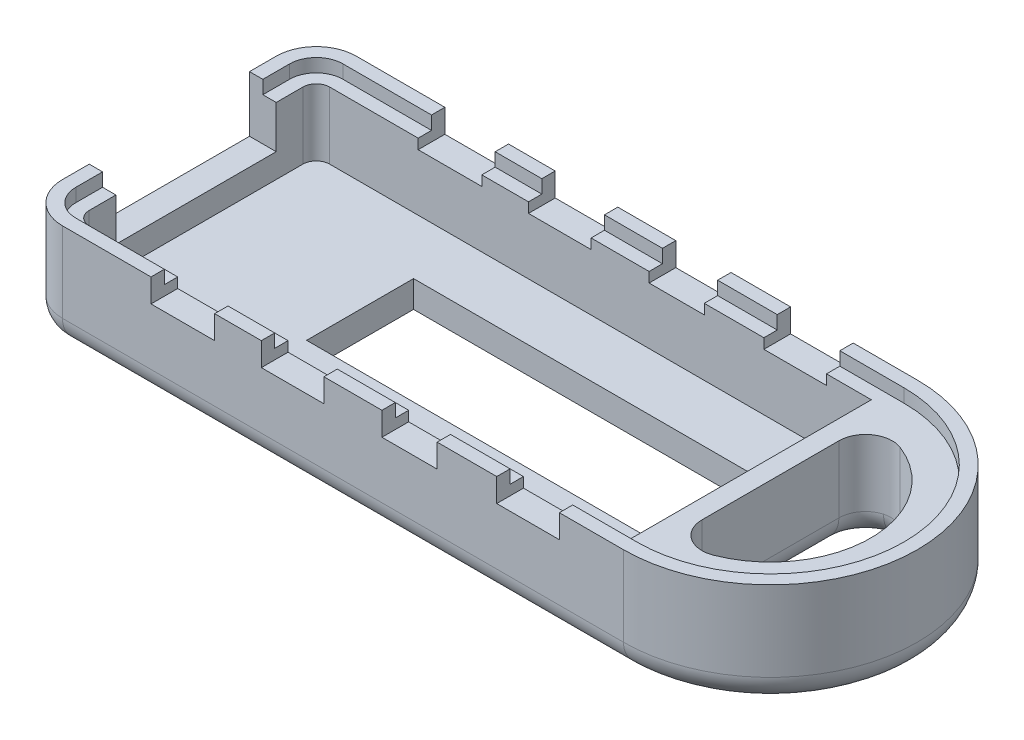
SolidWorks part; units mm, degrees
material "ABS"
ref_plane "Спереди" through (0, 0, 0) normal (0, 0, 1) x (1, 0, 0)
ref_plane "Сверху" through (0, 0, 0) normal (0, 1, 0) x (1, 0, 0)
ref_plane "Справа" through (0, 0, 0) normal (1, 0, 0) x (0, 0, -1)
sketch "Эскиз1" plane through (0, 0, 0) normal (0, 1, 0) x (1, 0, 0)
  line L0 (6.6974, 8.3377) -> (6.6974, -13.6623) construction
  line L1 (-35.3026, 8.3377) -> (6.6974, 8.3377)
  line L2 (-38.3026, 5.3377) -> (-38.3026, -10.6623)
  line L3 (-35.3026, -13.6623) -> (6.6974, -13.6623)
  arc A1 (-38.3026, -10.6623) -> (-35.3026, -13.6623) centre (-35.3026, -10.6623) ccw
  arc A2 (-38.3026, 5.3377) -> (-35.3026, 8.3377) centre (-35.3026, 5.3377) cw
  arc A4 (6.6974, 8.3377) -> (6.6974, -13.6623) centre (6.6974, -2.6623) cw
  point P3 (0, 0)
  point P5 (0, 0)
  point P6 (12.6974, -13.6623)
  point P9 (-38.3026, -13.6623)
  point P12 (-38.3026, 8.3377)
  point P14 (0, 0)
  dimension "D1" = 45
  dimension "D2" = 22
extrude "Бобышка-Вытянуть1" add sketch "Эскиз1" along normal blind 7
sketch "Эскиз2" plane through (0, 7, 0) normal (0, 1, 0) x (1, 0, 0)
  line L8 (-36.3026, 5.3377) -> (-36.3026, -10.6623)
  line L9 (-35.3026, -11.6623) -> (6.6974, -11.6623)
  line L11 (6.6974, 6.3377) -> (-35.3026, 6.3377)
  line L12 (-36.3026, 5.3377) -> (-36.3026, -10.6623)
  line L13 (-35.3026, -11.6623) -> (6.6974, -11.6623)
  line L15 (6.6974, 6.3377) -> (-35.3026, 6.3377)
  arc A3 (6.6974, -11.6623) -> (6.6974, 6.3377) centre (6.6974, -2.6623) ccw
  arc A4 (6.6974, -11.6623) -> (6.6974, 6.3377) centre (6.6974, -2.6623) ccw
  arc A8 (-35.3026, 6.3377) -> (-36.3026, 5.3377) centre (-35.3026, 5.3377) ccw
  arc A9 (-35.3026, 6.3377) -> (-36.3026, 5.3377) centre (-35.3026, 5.3377) ccw
  arc A10 (-36.3026, -10.6623) -> (-35.3026, -11.6623) centre (-35.3026, -10.6623) ccw
  arc A11 (-36.3026, -10.6623) -> (-35.3026, -11.6623) centre (-35.3026, -10.6623) ccw
  dimension "D1" = 2
extrude "Вырез-Вытянуть1" cut sketch "Эскиз2" against normal blind 5
sketch "Эскиз3" plane through (0, 2, 0) normal (0, 1, 0) x (1, 0, 0)
  line L0 (6.6974, 8.3377) -> (6.6974, -13.6623) construction
  line L1 (-24.7416, 2.0578) -> (1.7446, 2.0578)
  line L2 (-24.7416, 2.0578) -> (-24.7416, -5.9479)
  line L3 (-24.7416, -5.9479) -> (1.7446, -5.9479)
  line L4 (1.7446, 2.0578) -> (1.7446, -5.9479)
  line L5 (6.6974, 2.4612) -> (6.6974, -7.7858)
  arc A3 (9.4246, 4.3243) -> (9.4246, -9.6488) centre (6.6974, -2.6623) cw
  arc A5 (6.6974, -7.7858) -> (9.4246, -9.6488) centre (8.6974, -7.7858) ccw
  arc A6 (6.6974, 2.4612) -> (9.4246, 4.3243) centre (8.6974, 2.4612) cw
  point P11 (6.6974, -10.1623)
  point P16 (6.6974, 4.8377)
  dimension "D1" = 7.5
  dimension "D2" = 2
sketch "Эскиз4" plane through (-38.3026, 0, 0) normal (-1, 0, 0) x (0, 0, 1)
  line L0 (-3.3377, 7) -> (-3.3377, 3.8061)
  line L1 (-5.3377, 7) -> (10.6623, 7) construction
  line L2 (-3.3377, 3.8061) -> (8.6623, 3.8061)
  line L3 (8.6623, 3.8061) -> (8.6623, 7)
  line L4 (2.6623, 0) -> (2.6623, 7) construction
  line L5 (-5.3377, 0) -> (10.6623, 0) construction
  point P10 (2.6623, 3.8061)
  point P11 (-3.3377, 5.4031)
  dimension "D1" = 12
extrude "Вырез-Вытянуть3" cut sketch "Эскиз3" against normal blind 8
extrude "Вырез-Вытянуть4" cut sketch "Эскиз4" against normal blind 10 and the other way through all
sketch "Эскиз5" plane through (0, 2, 0) normal (0, 1, 0) x (1, 0, 0)
  line L1 (6.6974, 6.3377) -> (-35.3026, 6.3377) construction
  line L2 (-35.3026, -11.6623) -> (6.6974, -11.6623) construction
  line L3 (5.2536, 6.3377) -> (5.2536, -11.6623)
  line L5 (6.6974, 6.3377) -> (5.2536, 6.3377)
  line L6 (6.6974, 2.4612) -> (6.6974, -7.7858)
  line L7 (6.6974, 2.4612) -> (6.6974, -7.7858)
  line L8 (6.6974, -11.6623) -> (5.2536, -11.6623)
  arc A3 (6.6974, -11.6623) -> (6.6974, 6.3377) centre (6.6974, -2.6623) ccw
  arc A4 (6.6974, -11.6623) -> (6.6974, 6.3377) centre (6.6974, -2.6623) ccw
  arc A10 (6.6974, -7.7858) -> (9.4246, -9.6488) centre (8.6974, -7.7858) ccw
  arc A11 (9.4246, 4.3243) -> (6.6974, 2.4612) centre (8.6974, 2.4612) ccw
  arc A12 (9.4246, -9.6488) -> (9.4246, 4.3243) centre (6.6974, -2.6623) ccw
  arc A13 (6.6974, -7.7858) -> (9.4246, -9.6488) centre (8.6974, -7.7858) ccw
  arc A14 (9.4246, 4.3243) -> (6.6974, 2.4612) centre (8.6974, 2.4612) ccw
  arc A15 (9.4246, -9.6488) -> (9.4246, 4.3243) centre (6.6974, -2.6623) ccw
  dimension "D1" = 0
  dimension "D2" = 0
extrude "Бобышка-Вытянуть2" add sketch "Эскиз5" along normal blind 5
sketch "Эскиз6" plane through (0, 7, 0) normal (0, 1, 0) x (1, 0, 0)
  line L4 (-37.3026, -8.6623) -> (-37.3026, -10.6623)
  line L5 (-35.3026, -12.6623) -> (6.6974, -12.6623)
  line L6 (6.6974, 7.3377) -> (-35.3026, 7.3377)
  line L7 (-37.3026, 5.3377) -> (-37.3026, 3.3377)
  line L8 (-38.3026, -8.6623) -> (-38.3026, -10.6623)
  line L9 (-38.3026, 5.3377) -> (-38.3026, 3.3377)
  line L10 (6.6974, 8.3377) -> (-35.3026, 8.3377)
  line L11 (-35.3026, -13.6623) -> (6.6974, -13.6623)
  line L12 (-38.3026, -8.6623) -> (-38.3026, -10.6623)
  line L13 (-38.3026, 5.3377) -> (-38.3026, 3.3377)
  line L14 (6.6974, 8.3377) -> (-35.3026, 8.3377)
  line L15 (-35.3026, -13.6623) -> (6.6974, -13.6623)
  line L16 (-37.3026, -8.6623) -> (-38.3026, -8.6623)
  line L17 (-37.3026, 3.3377) -> (-38.3026, 3.3377)
  arc A3 (-37.3026, -10.6623) -> (-35.3026, -12.6623) centre (-35.3026, -10.6623) ccw
  arc A4 (6.6974, -12.6623) -> (6.6974, 7.3377) centre (6.6974, -2.6623) ccw
  arc A5 (-35.3026, 7.3377) -> (-37.3026, 5.3377) centre (-35.3026, 5.3377) ccw
  arc A6 (-38.3026, -10.6623) -> (-35.3026, -13.6623) centre (-35.3026, -10.6623) ccw
  arc A7 (-35.3026, 8.3377) -> (-38.3026, 5.3377) centre (-35.3026, 5.3377) ccw
  arc A8 (6.6974, -13.6623) -> (6.6974, 8.3377) centre (6.6974, -2.6623) ccw
  arc A9 (-38.3026, -10.6623) -> (-35.3026, -13.6623) centre (-35.3026, -10.6623) ccw
  arc A10 (-35.3026, 8.3377) -> (-38.3026, 5.3377) centre (-35.3026, 5.3377) ccw
  arc A11 (6.6974, -13.6623) -> (6.6974, 8.3377) centre (6.6974, -2.6623) ccw
  dimension "D1" = 0
  dimension "D2" = 1
extrude "Бобышка-Вытянуть3" add sketch "Эскиз6" along normal blind 1
sketch "Эскиз7" plane through (0, 0, 13.6623) normal (0, 0, 1) x (1, 0, 0)
  line L0 (-35.3026, 8) -> (6.6974, 8) construction
  line L1 (1.894, 8) -> (-2.7926, 8)
  line L2 (1.894, 8) -> (1.894, 6.2483)
  line L3 (1.894, 6.2483) -> (-2.7926, 6.2483)
  line L4 (-2.7926, 8) -> (-2.7926, 6.2483)
  line L6 (-7.2552, 8) -> (-11.3868, 8)
  line L7 (-7.2552, 8) -> (-7.2552, 6.2483)
  line L8 (-7.2552, 6.2483) -> (-11.3868, 6.2483)
  line L9 (-11.3868, 8) -> (-11.3868, 6.2483)
  line L10 (-15.7292, 8) -> (-20.4158, 8)
  line L11 (-15.7292, 8) -> (-15.7292, 6.2483)
  line L12 (-15.7292, 6.2483) -> (-20.4158, 6.2483)
  line L13 (-20.4158, 8) -> (-20.4158, 6.2483)
  line L14 (-23.9112, 8) -> (-28.6756, 8)
  line L15 (-23.9112, 8) -> (-23.9112, 6.2483)
  line L16 (-23.9112, 6.2483) -> (-28.6756, 6.2483)
  line L17 (-28.6756, 8) -> (-28.6756, 6.2483)
extrude "Вырез-Вытянуть5" cut sketch "Эскиз7" against normal through all both and the other way through all
fillet "Скругление1" radius 2 6 edges at (-37.424, 0, 12.7836) (-38.3026, 0, 2.6623) (-37.424, 0, -7.459) (-14.3026, 0, -8.3377) (17.6974, 0, 2.6623) (-14.3026, 0, 13.6623)
fillet "Скругление3" radius 2 3 edges at (7.5692, 0, -4.1126) (6.6974, 0, 2.6623) (7.5692, 0, 9.4372)
